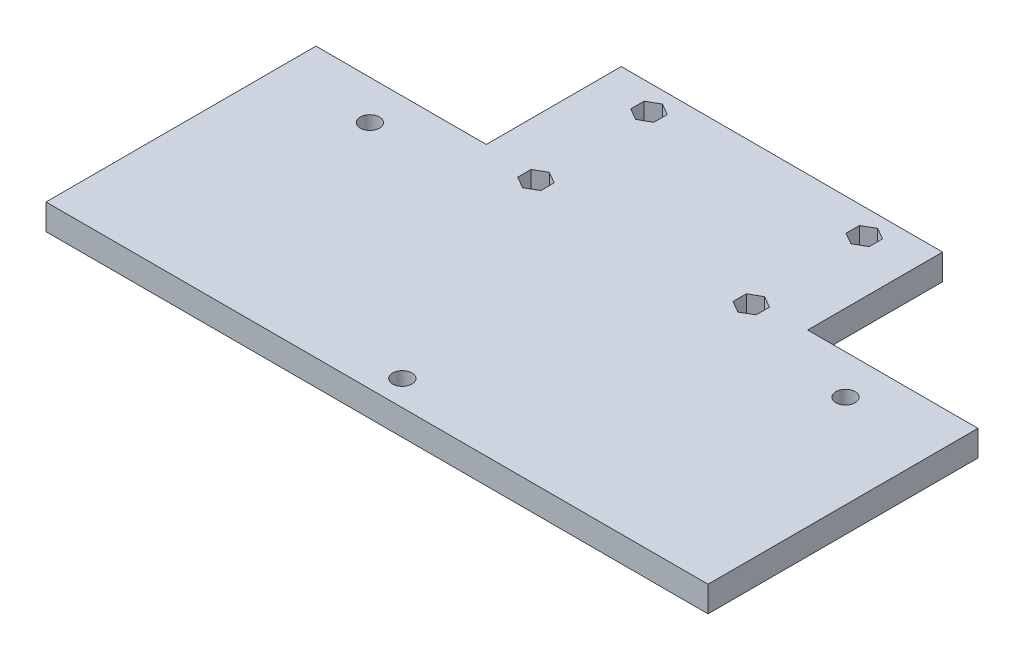
SolidWorks part; units mm, degrees
ref_plane "Front Plane" through (0, 0, 0) normal (0, 0, 1) x (1, 0, 0)
ref_plane "Top Plane" through (0, 0, 0) normal (0, 1, 0) x (1, 0, 0)
ref_plane "Right Plane" through (0, 0, 0) normal (1, 0, 0) x (0, 0, -1)
sketch "Sketch1" plane through (0, 0, 0) normal (0, 1, 0) x (1, 0, 0)
  line L0 (-47.6178, 3.1383) -> (55.3822, 3.1383) construction
  line L1 (-47.6178, 13.1383) -> (-21.1178, 13.1383)
  line L2 (-47.6178, 13.1383) -> (-47.6178, -28.8617)
  line L3 (-47.6178, -28.8617) -> (55.3822, -28.8617)
  line L4 (55.3822, 13.1383) -> (55.3822, -28.8617)
  line L5 (-47.6178, -18.8617) -> (55.3822, -18.8617) construction
  line L6 (-47.6178, -7.8617) -> (55.3822, -7.8617) construction
  line L7 (3.8822, 11.1383) -> (3.8822, -28.8617) construction
  line L8 (-21.1178, 13.1383) -> (-21.1178, 34.1383)
  line L9 (-21.1178, 34.1383) -> (28.8822, 34.1383)
  line L10 (28.8822, 34.1383) -> (28.8822, 13.1383)
  line L11 (28.8822, 13.1383) -> (55.3822, 13.1383)
  line L12 (3.8822, 34.1383) -> (3.8822, 11.1383) construction
  line L14 (-11.0603, 31.2289) -> (-12.8528, 32.2811)
  line L15 (-12.8528, 32.2811) -> (-14.6602, 31.255)
  line L16 (-14.6602, 31.255) -> (-14.6753, 29.1766)
  line L17 (-14.6753, 29.1766) -> (-12.8829, 28.1243)
  line L18 (-12.8829, 28.1243) -> (-11.0754, 29.1505)
  line L19 (-11.0754, 29.1505) -> (-11.0603, 31.2289)
  line L20 (20.6322, 28.1243) -> (22.4322, 29.1635)
  line L21 (22.4322, 29.1635) -> (22.4322, 31.2419)
  line L22 (22.4322, 31.2419) -> (20.6322, 32.2812)
  line L23 (20.6322, 32.2812) -> (18.8322, 31.2419)
  line L24 (18.8322, 31.2419) -> (18.8322, 29.1635)
  line L25 (18.8322, 29.1635) -> (20.6322, 28.1243)
  line L26 (-12.4651, 10.1288) -> (-10.6651, 11.168)
  line L27 (-10.6651, 11.168) -> (-10.6651, 13.2465)
  line L28 (-10.6651, 13.2465) -> (-12.4651, 14.2857)
  line L29 (-12.4651, 14.2857) -> (-14.2651, 13.2465)
  line L30 (-14.2651, 13.2465) -> (-14.2651, 11.168)
  line L31 (-14.2651, 11.168) -> (-12.4651, 10.1288)
  line L32 (21.0349, 10.1288) -> (22.8349, 11.168)
  line L33 (22.8349, 11.168) -> (22.8349, 13.2465)
  line L34 (22.8349, 13.2465) -> (21.0349, 14.2857)
  line L35 (21.0349, 14.2857) -> (19.2349, 13.2465)
  line L36 (19.2349, 13.2465) -> (19.2349, 11.168)
  line L37 (19.2349, 11.168) -> (21.0349, 10.1288)
  circle A0 centre (-33.1178, 7.0284) radius 1.5
  circle A1 centre (40.8822, 7.0284) radius 1.5
  circle A2 centre (3.8822, -24.9268) radius 1.5
  circle A3 centre (20.6322, 30.2027) radius 1.8 construction
  circle A7 centre (-12.8678, 30.2027) radius 1.8 construction
  circle A8 centre (-12.4651, 12.2072) radius 1.8 construction
  circle A9 centre (21.0349, 12.2072) radius 1.8 construction
  point P23 (0, 0)
  dimension "D5" = 37
  dimension "D6" = 3
  dimension "D7" = 50
  dimension "D8" = 3.6
  dimension "D11" = 21
  dimension "D1" = 103
  dimension "D2" = 42
  dimension "D3" = 22
  dimension "D4" = 11
  dimension "D9" = 33.5
  dimension "D10" = 18
  dimension "D12" = 33.5
extrude "Boss-Extrude1" add sketch "Sketch1" along normal blind 4
